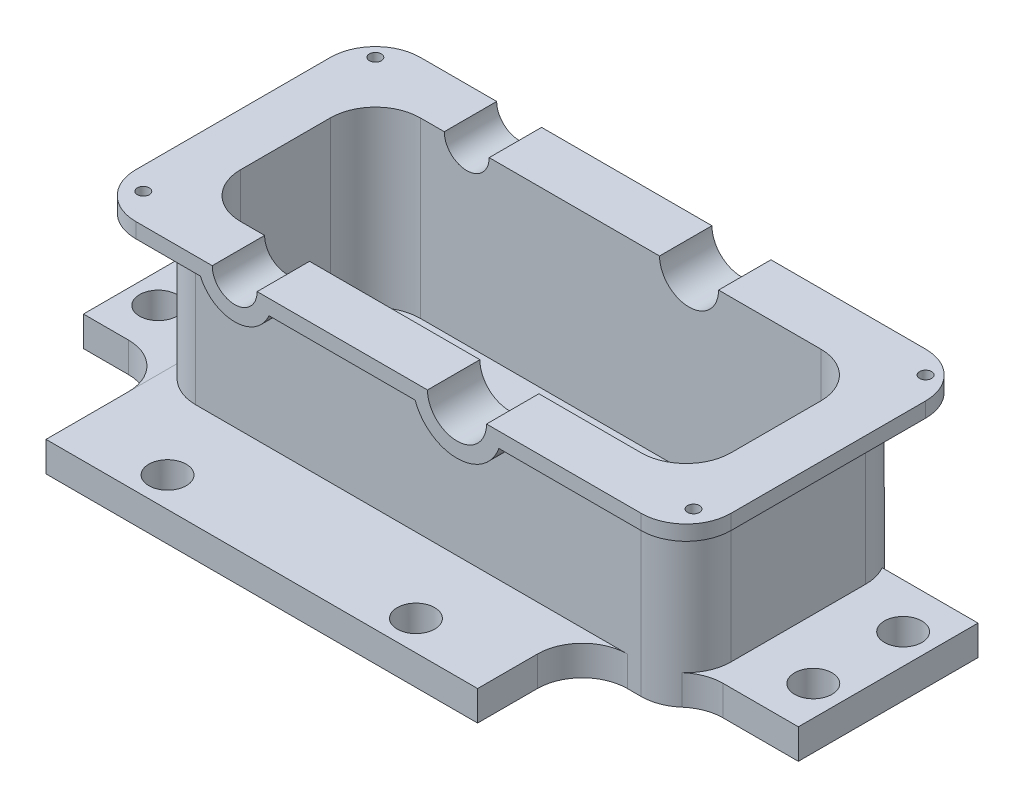
SolidWorks part; units mm, degrees
ref_plane "前视基准面" through (0, 0, 0) normal (0, 0, 1) x (1, 0, 0)
ref_plane "上视基准面" through (0, 0, 0) normal (0, 1, 0) x (1, 0, 0)
ref_plane "右视基准面" through (0, 0, 0) normal (1, 0, 0) x (0, 0, -1)
other "Configuration Table"
ref_plane "基准面1" through (-332.2628, 523.7381, -152.5) normal (0, 0, -1) x (-1, 0, 0)
sketch "草图2" plane through (0, 370, 0) normal (0, 1, 0) x (1, 0, 0)
  line L0 (-1120, 100) -> (5, 100) construction
  line L1 (-661.1779, 250) -> (-303.624, 250)
  line L2 (-661.1779, 250) -> (-661.1779, 100)
  line L3 (-661.1779, 100) -> (-303.624, 100)
  line L4 (-303.624, 250) -> (-303.624, 100)
  dimension "D1" = 150
extrude "凸台-拉伸1" add sketch "草图2" along normal blind 10
sketch "草图3" plane through (0, 380, 0) normal (0, 1, 0) x (1, 0, 0)
  line L0 (-646.1779, 235) -> (-646.1779, 115)
  line L1 (-661.1779, 250) -> (-303.624, 250)
  line L2 (-661.1779, 250) -> (-661.1779, 100)
  line L3 (-661.1779, 100) -> (-303.624, 100)
  line L4 (-303.624, 250) -> (-303.624, 100)
  line L5 (-646.1779, 115) -> (-318.624, 115)
  line L6 (-318.624, 235) -> (-318.624, 115)
  line L7 (-646.1779, 235) -> (-318.624, 235)
  dimension "D1" = 15
extrude "凸台-拉伸2" add sketch "草图3" along normal blind 140
sketch "草图4" plane through (0, 0, -250) normal (0, 0, -1) x (-1, 0, 0)
  line L1 (436.64, 496) -> (179.513, 496)
  line L3 (436.64, 596.7404) -> (179.513, 596.7404)
  line L4 (179.513, 496) -> (179.513, 596.7404)
  line L5 (436.64, 496) -> (733.1869, 496)
  line L7 (436.64, 596.7404) -> (733.1869, 596.7404)
  line L8 (733.1869, 496) -> (733.1869, 596.7404)
extrude "切除-拉伸1" cut sketch "草图4" against normal through all both and the other way through all
sketch "草图5" plane through (0, 0, -250) normal (0, 0, -1) x (-1, 0, 0)
  circle A0 centre (436.64, 496) radius 19.7138
extrude "切除-拉伸2" cut sketch "草图5" against normal through all both and the other way through all
sketch "草图6" plane through (0, 370, 0) normal (0, -1, 0) x (-1, 0, 0)
  line L0 (661.1779, 100) -> (303.624, 100) construction
  line L1 (372.89, 100) -> (661.1779, 100)
  line L2 (372.89, 100) -> (372.89, 30)
  line L3 (372.89, 30) -> (661.1779, 30)
  line L4 (661.1779, 100) -> (661.1779, 30)
  circle A0 centre (600, 50) radius 12.5 construction
  circle A1 centre (434.07, 50) radius 12.5 construction
  dimension "D3" = 20
  dimension "D1" = 61.1779
  dimension "D2" = 61.18
extrude "凸台-拉伸3" add sketch "草图6" against normal blind 20
sketch "草图7" plane through (0, 390, 0) normal (0, 1, 0) x (1, 0, 0)
  circle A0 centre (-600, 50) radius 12.5
  circle A1 centre (-434.07, 50) radius 12.5
extrude "切除-拉伸3" cut sketch "草图7" against normal through all both and the other way through all
sketch "草图8" plane through (0, 0, -250) normal (0, 0, -1) x (-1, 0, 0)
  circle A0 centre (585.14, 496) radius 15
  dimension "D1" = 30
extrude "切除-拉伸4" cut sketch "草图8" against normal through all both and the other way through all
sketch "草图10" plane through (0, 370, 0) normal (0, -1, 0) x (1, 0, 0)
  line L0 (-661.1779, -100) -> (-661.1779, -250) construction
  line L1 (-661.1779, -235) -> (-721.1779, -235)
  line L2 (-661.1779, -235) -> (-661.1779, -115)
  line L3 (-661.1779, -115) -> (-721.1779, -115)
  line L4 (-721.1779, -235) -> (-721.1779, -115)
  line L5 (-303.624, -250) -> (-303.624, -100) construction
  line L6 (-303.624, -235) -> (-243.624, -235)
  line L7 (-303.624, -235) -> (-303.624, -115)
  line L8 (-303.624, -115) -> (-243.624, -115)
  line L9 (-243.624, -235) -> (-243.624, -115)
  line L10 (-318.624, -115) -> (-416.9262, -115) construction
  line L11 (-416.9262, -235) -> (-318.624, -235) construction
  line L12 (-318.624, -235) -> (-646.1779, -235) construction
  line L13 (-646.1779, -115) -> (-318.624, -115) construction
  dimension "D1" = 60
  dimension "D2" = 60
extrude "凸台-拉伸5" add sketch "草图10" against normal blind 20
fillet "圆角4" radius 30 4 edges at (-303.624, 433, -250) (-303.624, 433, -100) (-661.1779, 433, -250) (-661.1779, 443, -100)
fillet "圆角5" radius 30 4 edges at (-646.1779, 438, -115) (-318.624, 438, -115) (-318.624, 438, -235) (-646.1779, 438, -235)
fillet "圆角6" radius 30 2 edges at (-372.89, 380, -100) (-661.1779, 380, -115)
fillet "圆角7" radius 30 1 edges at (-307.6432, 380, -115)
fillet "圆角8" radius 30 1 edges at (-657.1587, 380, -235)
sketch "草图11" plane through (0, 496, 0) normal (0, 1, 0) x (1, 0, 0)
  line L0 (-681.1779, 240) -> (-681.1779, 110)
  line L3 (-651.1779, 80) -> (-313.624, 80)
  line L4 (-681.1779, 80) -> (-283.624, 80) construction
  line L5 (-283.624, 270) -> (-283.624, 80) construction
  line L7 (-303.624, 250) -> (-303.624, 100) construction
  line L8 (-661.1779, 100) -> (-303.624, 100) construction
  line L9 (-661.1779, 250) -> (-303.624, 250) construction
  line L10 (-681.1779, 270) -> (-283.624, 270) construction
  line L11 (-681.1779, 270) -> (-681.1779, 80) construction
  line L15 (-661.1779, 250) -> (-661.1779, 100) construction
  line L52 (-283.624, 240) -> (-283.624, 110)
  line L61 (-456.3538, 250) -> (-456.3538, 235)
  line L62 (-456.3538, 235) -> (-416.9262, 235)
  line L63 (-416.9262, 235) -> (-416.9262, 250)
  line L64 (-416.9262, 250) -> (-456.3538, 250)
  line L68 (-416.9262, 250) -> (-456.3538, 250)
  line L85 (-651.1779, 270) -> (-313.624, 270)
  line L87 (-631.1779, 250) -> (-333.624, 250)
  line L88 (-661.1779, 220) -> (-661.1779, 130)
  line L89 (-631.1779, 100) -> (-333.624, 100)
  line L90 (-303.624, 220) -> (-303.624, 130)
  arc A3 (-313.624, 80) -> (-283.624, 110) centre (-313.624, 110) ccw
  arc A4 (-303.624, 130) -> (-333.624, 100) centre (-333.624, 130) cw
  arc A5 (-333.624, 250) -> (-303.624, 220) centre (-333.624, 220) cw
  arc A12 (-283.624, 240) -> (-313.624, 270) centre (-313.624, 240) ccw
  arc A15 (-681.1779, 240) -> (-651.1779, 270) centre (-651.1779, 240) cw
  arc A20 (-661.1779, 220) -> (-631.1779, 250) centre (-631.1779, 220) cw
  arc A21 (-681.1779, 110) -> (-651.1779, 80) centre (-651.1779, 110) ccw
  arc A22 (-661.1779, 130) -> (-631.1779, 100) centre (-631.1779, 130) ccw
  line M57 (-600.14, 250) -> (-631.1779, 250)
  arc M58 (-631.1779, 250) -> (-661.1779, 220) centre (-631.1779, 220) ccw
  line M59 (-661.1779, 220) -> (-661.1779, 130)
  arc M60 (-661.1779, 130) -> (-631.1779, 100) centre (-631.1779, 130) ccw
  line M61 (-631.1779, 100) -> (-600.14, 100)
  dimension "D1" = 30
  dimension "D6" = 0
  dimension "D9" = 20
extrude "凸台-拉伸6" add sketch "草图11" against normal blind 10 contours L0 A21 L3 A3 L52 A12 L85 A15 L87 A5 L90 A4 L89 L68 M61 M60 M59 M58 M57 region at (-669.2754, 496, -258.0975)
sketch "草图12" plane through (0, 0, -235) normal (0, 0, 1) x (1, 0, 0)
  line L0 (-456.3538, 496) -> (-416.9262, 496) construction
  circle A0 centre (-585.14, 496) radius 15
  circle A1 centre (-436.64, 496) radius 19.7138
extrude "切除-拉伸5" cut sketch "草图12" against normal through all both and the other way through all
sketch "草图13" plane through (0, 0, -100) normal (0, 0, 1) x (1, 0, 0)
  circle A0 centre (-585.14, 496) radius 15
  circle A1 centre (-585.14, 496) radius 25
  circle A2 centre (-436.64, 496) radius 19.7138
  circle A3 centre (-436.64, 496) radius 29.7138
  dimension "D1" = 10
  dimension "D2" = 10
extrude "凸台-拉伸7" add sketch "草图13" along normal up to surface (20 mm away) up to face at (-624.9346, 490.9119, -80)
sketch "草图14" plane through (0, 0, -80) normal (0, 0, 1) x (1, 0, 0)
  line L0 (-610.14, 496) -> (-557.3832, 496)
  line L1 (-560.14, 496) -> (-466.3538, 496) construction
  line L2 (-557.3832, 496) -> (-557.3832, 534.2514)
  line L3 (-557.3832, 534.2514) -> (-607.38, 534.2514)
  line L5 (-610.14, 496) -> (-621.5341, 496)
  line L6 (-651.1779, 496) -> (-610.14, 496) construction
  line L7 (-621.5341, 496) -> (-621.5341, 534.2514)
  line L8 (-621.5341, 534.2514) -> (-606.2703, 534.2514)
  arc M7 (-560.14, 496) -> (-610.14, 496) centre (-585.14, 496) ccw
  circle M18 centre (-585.14, 496) radius 15
extrude "切除-拉伸7" cut sketch "草图14" against normal through all both and the other way through all contours L0 M7 M18 region at (-585.14, 511.559, -80)
sketch "草图15" plane through (0, 0, -80) normal (0, 0, 1) x (1, 0, 0)
  line L0 (-483.5192, 496) -> (-384.813, 496)
  line L1 (-570.14, 496) -> (-466.3538, 496) construction
  line L2 (-384.813, 496) -> (-391.3809, 542.1813)
  line L3 (-391.3809, 542.1813) -> (-485.3958, 523.4159)
  line L4 (-485.3958, 523.4159) -> (-483.5192, 496)
extrude "切除-拉伸8" cut sketch "草图15" against normal through all both and the other way through all
sketch "草图16" plane through (0, 0, -250) normal (0, 0, -1) x (-1, 0, 0)
  circle A0 centre (436.64, 496) radius 19.7138
  circle A1 centre (436.64, 496) radius 29.7138
  circle A2 centre (585.14, 496) radius 15
  circle A3 centre (585.14, 496) radius 25
  dimension "D1" = 10
  dimension "D2" = 10
extrude "凸台-拉伸8" add sketch "草图16" along normal up to surface (20 mm away) contours A1 | A3 up to face at (-365.789, 490.9544, -270)
sketch "草图17" plane through (0, 0, -100) normal (0, 0, 1) x (1, 0, 0)
  circle A0 centre (-585.14, 496) radius 15
  circle A1 centre (-436.64, 496) radius 19.7138
extrude "切除-拉伸9" cut sketch "草图17" against normal through all both and the other way through all
sketch "草图18" plane through (0, 0, -250) normal (0, 0, -1) x (-1, 0, 0)
  line L0 (376.6409, 496) -> (644.8521, 496)
  line L1 (406.9262, 496) -> (313.624, 496) construction
  line L2 (651.1779, 496) -> (610.14, 496) construction
  line L3 (644.8521, 496) -> (631.9894, 582.4389)
  line L4 (631.9894, 582.4389) -> (371.3588, 543.6553)
  line L5 (371.3588, 543.6553) -> (376.6409, 496)
extrude "切除-拉伸10" cut sketch "草图18" against normal through all both and the other way through all
sketch "草图19" plane through (0, 496, 0) normal (0, 1, 0) x (1, 0, 0)
  circle A0 centre (-666.1779, 255) radius 4
  circle A1 centre (-666.1779, 100) radius 4
  circle A2 centre (-298.624, 100) radius 4
  circle A3 centre (-298.624, 255) radius 4
extrude "切除-拉伸11" cut sketch "草图19" against normal blind 50 and the other way through all
sketch "草图20" plane through (0, 390, 0) normal (0, 1, 0) x (1, 0, 0)
  line L0 (-721.1779, 235) -> (-681.1779, 235) construction
  line L1 (-681.1779, 240) -> (-681.1779, 110) construction
  line L2 (-721.1779, 235) -> (-670.8642, 235) construction
  line L3 (-701.1779, 245.5616) -> (-701.1779, 106.193) construction
  line L4 (-691.1779, 115) -> (-721.1779, 115) construction
  line L5 (-283.624, 235) -> (-243.624, 235) construction
  line L6 (-283.624, 240) -> (-283.624, 110) construction
  line L7 (-307.6432, 235) -> (-243.624, 235) construction
  line L8 (-263.624, 249.8045) -> (-263.624, 69.608) construction
  line L10 (-243.624, 115) -> (-293.9377, 115) construction
  circle A0 centre (-701.1779, 205) radius 12.5
  circle A1 centre (-701.1779, 145) radius 12.5
  circle A3 centre (-263.624, 205) radius 12.5
  circle A4 centre (-263.624, 145) radius 12.5
  dimension "D1" = 25
  dimension "D2" = 25
  dimension "D3" = 30
  dimension "D4" = 30
  dimension "D5" = 25
  dimension "D6" = 25
  dimension "D7" = 30
  dimension "D8" = 30
extrude "切除-拉伸12" cut sketch "草图20" against normal blind 70
